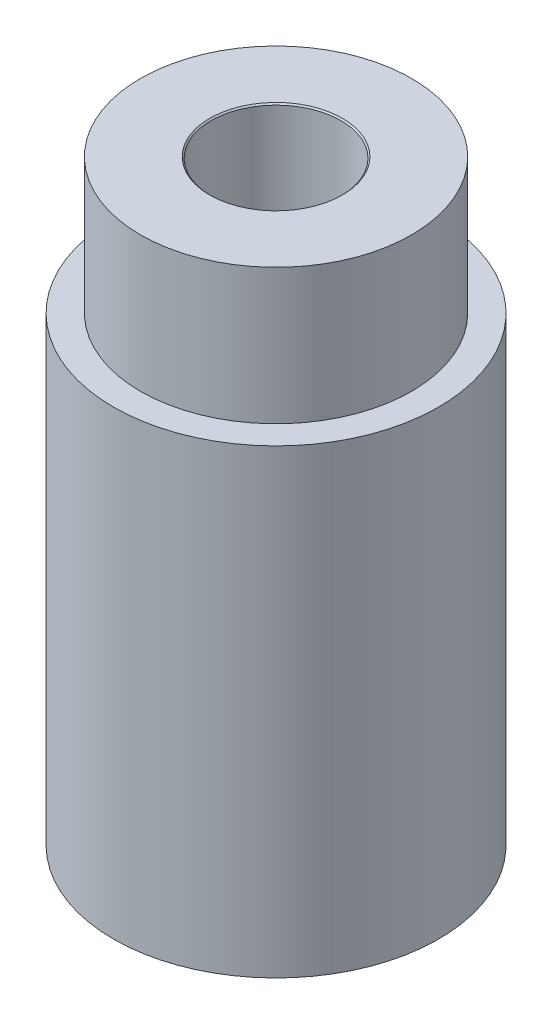
SolidWorks part; units mm, degrees
ref_plane "Front Plane" through (0, 0, 0) normal (0, 0, 1) x (1, 0, 0)
ref_plane "Top Plane" through (0, 0, 0) normal (0, 1, 0) x (1, 0, 0)
ref_plane "Right Plane" through (0, 0, 0) normal (1, 0, 0) x (0, 0, -1)
sketch "Sketch1" plane through (0, 0, 0) normal (0, 1, 0) x (1, 0, 0)
  circle A0 centre (0, 0) radius 3
  dimension "D1" = 6
extrude "Boss-Extrude1" add sketch "Sketch1" along normal blind 8.5
sketch "Sketch2" plane through (0, 8.5, 0) normal (0, 1, 0) x (1, 0, 0)
  circle A0 centre (0, 0) radius 2.5
  dimension "D1" = 5
extrude "Boss-Extrude2" add sketch "Sketch2" along normal blind 2.5
hole_wizard "M2 Clearance Hole1" positions "Sketch5" profile "Sketch4" hole size "M2" standard "ANSI Metric" end condition through all
sketch "Sketch5" plane through (0, 11, 0) normal (0, 1, 0) x (1, 0, 0)
  point P0 (0, 0)
sketch "Sketch4" plane through (0, 11, 0) normal (1, 0, 0) x (0, 0, 1)
  line L0 (0, 0) -> (0, 11)
  line L1 (0, 11) -> (1.2, 11)
  line L2 (1.2, 11) -> (1.2, 0.025)
  line L3 (1.2, 0.025) -> (1.225, 0)
  line L5 (1.225, 0) -> (0, 0)
  line L6 (-1.2, 0.025) -> (-1.225, 0) construction
  line L11 (0, -6.35) -> (0, 107.95) construction
  dimension "Thru Hole Dia." = 2.4
  dimension "Thru Hole Depth" = 11
  dimension "Near C'Sink Dia." = 2.45
  dimension "Near C'Sink Angle" = 90
